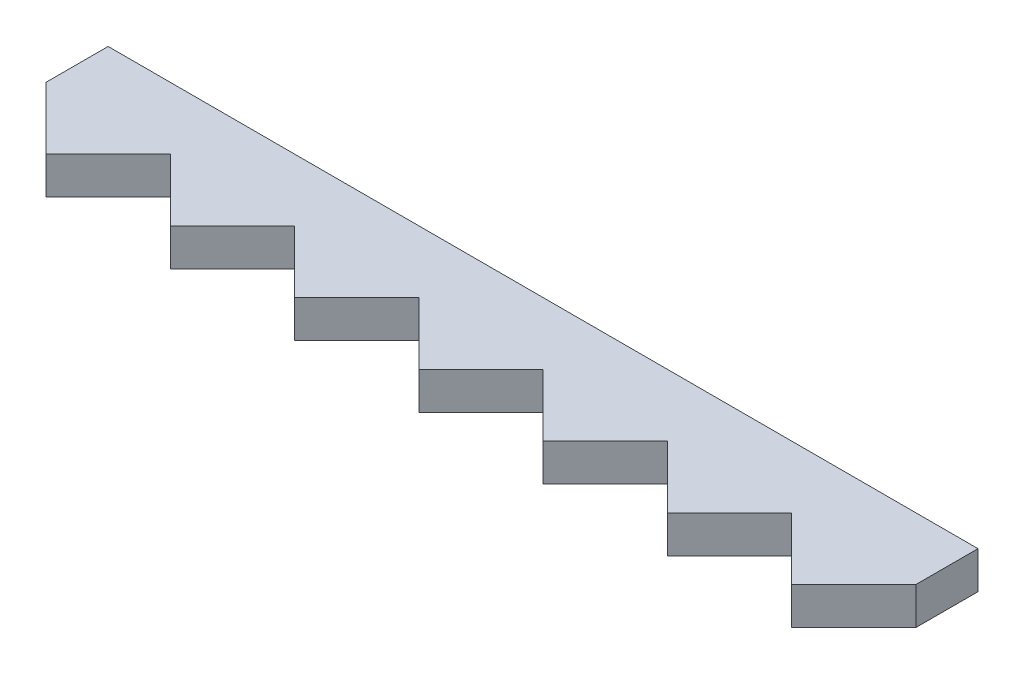
SolidWorks part; units mm, degrees
ref_plane "Front Plane" through (0, 0, 0) normal (0, 0, 1) x (1, 0, 0)
ref_plane "Top Plane" through (0, 0, 0) normal (0, 1, 0) x (1, 0, 0)
ref_plane "Right Plane" through (0, 0, 0) normal (1, 0, 0) x (0, 0, -1)
sketch "Sketch1" plane through (0, 3, 0) normal (0, 1, 0) x (1, 0, 0)
  line L0 (0, 32.1404) -> (0, 27.1404)
  line L1 (66, 32.1404) -> (-5, 32.1404) construction
  line L2 (0, 27.1404) -> (5, 22.1404)
  line L3 (5, 22.1404) -> (10, 27.1404)
  line L4 (5, 22.1404) -> (65, 22.1404) construction
  line L5 (0, 27.1404) -> (70, 27.1404) construction
  line L6 (70, 22.1404) -> (70, 46.1404) construction
  line L7 (10, 27.1404) -> (15, 22.1404)
  line L8 (15, 22.1404) -> (20, 27.1404)
  line L9 (20, 27.1404) -> (25, 22.1404)
  line L10 (25, 22.1404) -> (30, 27.1404)
  line L11 (30, 27.1404) -> (35, 22.1404)
  line L12 (35, 22.1404) -> (40, 27.1404)
  line L13 (40, 27.1404) -> (45, 22.1404)
  line L14 (45, 22.1404) -> (50, 27.1404)
  line L15 (50, 27.1404) -> (55, 22.1404)
  line L16 (55, 22.1404) -> (60, 27.1404)
  line L17 (60, 27.1404) -> (65, 22.1404)
  line L18 (65, 22.1404) -> (70, 27.1404)
  line L19 (0, 32.1404) -> (70, 32.1404)
  line L20 (70, 32.1404) -> (70, 27.1404)
  dimension "D1" = 5
  dimension "D2" = 5
  dimension "D3" = 10
  dimension "D4" = 7
extrude "Boss-Extrude1" add sketch "Sketch1" along normal blind 3
